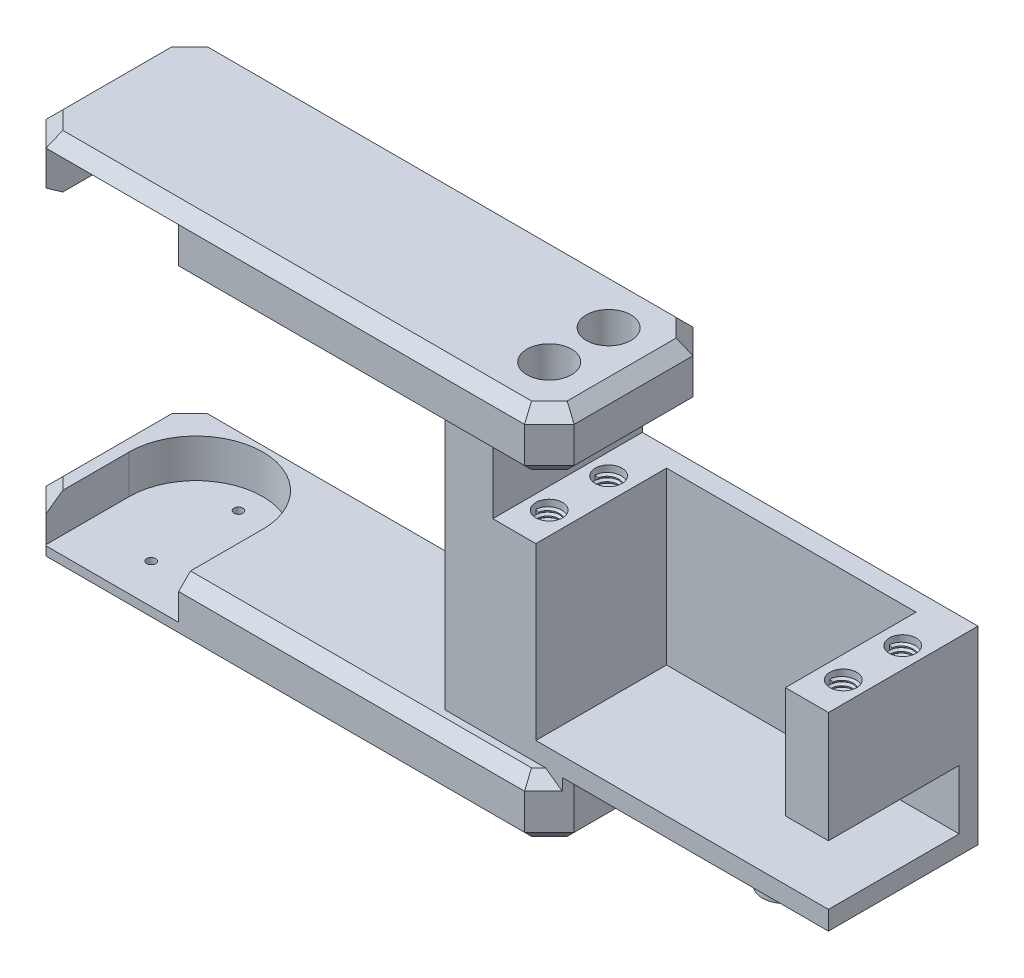
SolidWorks part; units mm, degrees
ref_plane "Front Plane" through (0, 0, 0) normal (0, 0, 1) x (1, 0, 0)
ref_plane "Top Plane" through (0, 0, 0) normal (0, 1, 0) x (1, 0, 0)
ref_plane "Right Plane" through (0, 0, 0) normal (1, 0, 0) x (0, 0, -1)
sketch "Sketch1" plane through (0, 0, 0) normal (0, 1, 0) x (1, 0, 0)
  line L0 (0, 11) -> (0, 14.175)
  line L1 (-21, -11) -> (21, -11) construction
  line L2 (-21, -11) -> (-21, 11)
  line L3 (-21, 11) -> (21, 11)
  line L4 (21, -11) -> (21, 11)
  line L5 (-21, -11) -> (21, 11) construction
  line L6 (-21, 11) -> (21, -11) construction
  line L7 (0, 0) -> (-20, 0) construction
  line L8 (-20, 0) -> (-27.25, 0) construction
  line L10 (-27.25, 14.175) -> (0, 14.175)
  line L11 (0, 0) -> (27.25, 0) construction
  line L13 (27.25, 14.175) -> (0, 14.175)
  line L14 (0, 14.175) -> (0, 16.3945)
  line L15 (0, 16.3945) -> (-24.75, 16.3945) construction
  line L16 (-24.75, 0) -> (-24.75, 5) construction
  line L17 (0, 16.3945) -> (24.75, 16.3945) construction
  line L18 (24.75, 0) -> (24.75, 5) construction
  line L19 (24.75, 0) -> (24.75, -5) construction
  line L20 (-24.75, 0) -> (-24.75, -5) construction
  line L22 (27.25, -11) -> (21, -11)
  line L25 (-27.25, -11) -> (-21, -11)
  line L27 (-28.25, 0) -> (-28.25, 14.175)
  line L28 (-28.25, 14.175) -> (-27.25, 14.175)
  line L29 (-27.25, -11) -> (-28.25, -11)
  line L30 (-28.25, -11) -> (-28.25, 0)
  line L31 (27.25, -11) -> (28.25, -11)
  line L32 (28.25, -11) -> (28.25, 0)
  line L33 (28.25, 0) -> (28.25, 14.175)
  line L34 (28.25, 14.175) -> (27.25, 14.175)
  point P0 (0, 0)
  dimension "D4" = 10
  dimension "D8" = 7.25
  dimension "D1" = 42
  dimension "D2" = 22
  dimension "D3" = 24.75
  dimension "D5" = 14.175
  dimension "D6" = 27.25
  dimension "D7" = 24.75
sketch "Sketch2" plane through (0, 0, 0) normal (0, 1, 0) x (1, 0, 0)
  line L0 (-27.25, -11) -> (27.25, -11)
  line L1 (27.25, -11) -> (27.25, 14.175)
  line L2 (27.25, 14.175) -> (-27.25, 14.175)
  line L3 (-27.25, 14.175) -> (-27.25, -11)
extrude "Boss-Extrude1" add sketch "Sketch2" along normal blind 3.175
extrude "Boss-Extrude2" add sketch "Sketch1" along normal blind 31.875
sketch "Sketch4" plane through (0, 31.875, 0) normal (0, 1, 0) x (1, 0, 0)
  line L0 (0, 0) -> (27.25, 0) construction
  line L1 (0, 0) -> (0, -11.8283) construction
  line L2 (0, -11.8283) -> (24.75, -11.8283) construction
  line L3 (24.75, 0) -> (24.75, -5) construction
  line L4 (24.75, 0) -> (24.75, 5) construction
  line L5 (0, 0) -> (-27.25, 0) construction
  line L6 (0, -11.8283) -> (-24.75, -11.8283) construction
  line L7 (-24.75, 0) -> (-24.75, -5) construction
  line L8 (-24.75, 0) -> (-24.75, 5) construction
  circle A0 centre (24.75, -5) radius 2.25
  circle A1 centre (24.75, 5) radius 2.25
  circle A2 centre (-24.75, -5) radius 2.25
  circle A3 centre (-24.75, 5) radius 2.25
  dimension "D1" = 24.75
extrude "Cut-Extrude1" cut sketch "Sketch4" against normal blind 12.7
thread "Thread1" pitch 0.7937 start angle 0, offset 1, length 0, pitch 0.7937, diameter 4.5
ref_plane "Plane1" through (-27, 30.875, -5) normal (0, 0, 1) x (-1, 0, 0)
sketch "Thread Profile1" plane through (-27, 30.875, -5) normal (0, 0, 1) x (-1, 0, 0)
  line L0 (0, 0) -> (0, 0.7937) construction
  line L11 (0, 0) -> (0, 0.6945)
  line L12 (0, 0.6945) -> (-0.4296, 0.4465)
  line L13 (-0.4296, 0.4465) -> (-0.4296, 0.248)
  line L15 (-0.4296, 0.248) -> (0, 0)
  line L17 (-0.4296, 0.3473) -> (0, 0.3473) construction
  point P2 (0, 0)
  dimension "Pitch" = 0.7937
  dimension "Profile_Angle" = 60
  dimension "Profile_Land" = 0.1984
  dimension "Profile_Height" = 0.4296
thread "Thread2" pitch 0.7937 profile "Thread Profile2" start angle 0, offset 1, length 0, pitch 0.7937, diameter 4.5
ref_plane "Plane2" through (-27, 30.875, 5) normal (0, 0, 1) x (-1, 0, 0)
sketch "Thread Profile2" plane through (-27, 30.875, 5) normal (0, 0, 1) x (-1, 0, 0)
  line L0 (0, 0) -> (0, 0.7937) construction
  line L11 (0, 0) -> (0, 0.6945)
  line L12 (0, 0.6945) -> (-0.4296, 0.4465)
  line L13 (-0.4296, 0.4465) -> (-0.4296, 0.248)
  line L15 (-0.4296, 0.248) -> (0, 0)
  line L17 (-0.4296, 0.3473) -> (0, 0.3473) construction
  point P2 (0, 0)
  dimension "Pitch" = 0.7937
  dimension "Profile_Angle" = 60
  dimension "Profile_Land" = 0.1984
  dimension "Profile_Height" = 0.4296
thread "Thread3" pitch 0.7937 profile "Thread Profile3" start angle 0, offset 1, length 0, pitch 0.7937, diameter 4.5
ref_plane "Plane3" through (22.5, 30.875, -5) normal (0, 0, 1) x (-1, 0, 0)
sketch "Thread Profile3" plane through (22.5, 30.875, -5) normal (0, 0, 1) x (-1, 0, 0)
  line L0 (0, 0) -> (0, 0.7937) construction
  line L11 (0, 0) -> (0, 0.6945)
  line L12 (0, 0.6945) -> (-0.4296, 0.4465)
  line L13 (-0.4296, 0.4465) -> (-0.4296, 0.248)
  line L15 (-0.4296, 0.248) -> (0, 0)
  line L17 (-0.4296, 0.3473) -> (0, 0.3473) construction
  point P2 (0, 0)
  dimension "Pitch" = 0.7937
  dimension "Profile_Angle" = 60
  dimension "Profile_Land" = 0.1984
  dimension "Profile_Height" = 0.4296
thread "Thread4" pitch 0.7937 profile "Thread Profile4" start angle 0, offset 1, length 0, pitch 0.7937, diameter 4.5
ref_plane "Plane4" through (22.5, 30.875, 5) normal (0, 0, 1) x (-1, 0, 0)
sketch "Thread Profile4" plane through (22.5, 30.875, 5) normal (0, 0, 1) x (-1, 0, 0)
  line L0 (0, 0) -> (0, 0.7937) construction
  line L11 (0, 0) -> (0, 0.6945)
  line L12 (0, 0.6945) -> (-0.4296, 0.4465)
  line L13 (-0.4296, 0.4465) -> (-0.4296, 0.248)
  line L15 (-0.4296, 0.248) -> (0, 0)
  line L17 (-0.4296, 0.3473) -> (0, 0.3473) construction
  point P2 (0, 0)
  dimension "Pitch" = 0.7937
  dimension "Profile_Angle" = 60
  dimension "Profile_Land" = 0.1984
  dimension "Profile_Height" = 0.4296
sketch "Sketch13" plane through (21, 0, 0) normal (-1, 0, 0) x (0, 0, 1)
  line L0 (11, 3.175) -> (11, 13.175)
  line L1 (11, 31.875) -> (11, 0) construction
  line L2 (11, 13.175) -> (-11, 13.175)
  line L3 (-11, 31.875) -> (-11, 3.175) construction
  line L4 (-11, 13.175) -> (-11, 3.175)
  line L5 (-11, 3.175) -> (11, 3.175)
  dimension "D1" = 10
extrude "Cut-Extrude2" cut sketch "Sketch13" against normal blind 12.7
sketch "Sketch14" plane through (0, 0, 0) normal (0, -1, 0) x (1, 0, 0)
  line L0 (20, 0) -> (9.9, 0) construction
  line L1 (20, 0) -> (20, 1.8391) construction
  circle A1 centre (9.9, 0) radius 3.75
  dimension "D1" = 7.5
extrude "Boss-Extrude3" add sketch "Sketch14" along normal blind 8
sketch "Sketch15" plane through (-28.25, 0, 0) normal (-1, 0, 0) x (0, 0, 1)
  line L4 (-14.175, 0) -> (11, 0)
  line L5 (11, 0) -> (-14.175, 0) construction
  line L6 (11, 31.875) -> (11, 0) construction
  line L11 (7.1008, 47.975) -> (0, 47.975) construction
  line L13 (0, 47.975) -> (0, -8) construction
  line L14 (-3.75, -8) -> (3.75, -8) construction
  line L15 (3.75, 0) -> (3.75, -8) construction
  line L17 (7.1008, 47.975) -> (9.7473, 47.975) construction
  line L21 (7.1008, 3.175) -> (7.1008, 47.975) construction
  line L22 (-11, 3.175) -> (11, 3.175) construction
  line L24 (9.7473, 47.975) -> (9.7473, 43.475) construction
  line L25 (9.7473, 43.475) -> (11, 43.475) construction
  line L26 (11, 43.475) -> (11, 0)
  line L27 (11, 43.475) -> (-14.175, 43.475)
  line L28 (-14.175, 43.475) -> (-14.175, 0)
  line L29 (3.75, -8) -> (3.75, 0) construction
  line L30 (0, 19.9875) -> (30.891, 19.9875) construction
  line L31 (7.1008, 3.175) -> (7.1008, 0) construction
  dimension "D1" = 4.5
  dimension "D5" = 3.175
  dimension "D2" = 55.975
  dimension "D3" = 44.8
  dimension "D4" = 8
extrude "Boss-Extrude4" add sketch "Sketch15" along normal blind 20 contours L28 L4 L26 L27
sketch "Sketch16" plane through (0, 43.475, 0) normal (0, 1, 0) x (1, 0, 0)
  line L0 (9.9, 0) -> (-28.25, 0) construction
  line L1 (-28.25, -11) -> (-28.25, 14.175) construction
  line L2 (-104.45, 0) -> (-15.55, 0) construction
  line L3 (-48.25, -11) -> (-48.25, 14.175) construction
  line L9 (-104.45, 0) -> (-104.45, 10)
  line L10 (-104.45, 0) -> (-104.45, -10)
  line L23 (-15.55, 0) -> (-15.55, 10)
  line L24 (-19.725, 14.175) -> (-100.275, 14.175)
  line L25 (-104.45, -10) -> (-100.275, -14.175)
  line L26 (-15.55, 10) -> (-19.725, 14.175)
  line L27 (-104.45, 10) -> (-100.275, 14.175)
  line L28 (-15.55, 0) -> (-15.55, -10)
  line L29 (-100.275, -14.175) -> (-19.725, -14.175)
  line L30 (-15.55, -10) -> (-19.725, -14.175)
  circle A0 centre (-48.25, 0) radius 11.25 construction
  circle A2 centre (9.9, 0) radius 11.25 construction
  dimension "D1" = 88.9
extrude "Boss-Extrude5" add sketch "Sketch16" along normal blind 10
sketch "Sketch20" plane through (0, 53.475, 0) normal (0, 1, 0) x (1, 0, 0)
  circle A0 centre (-24.75, 5) radius 3.75
  circle A1 centre (-24.75, -5) radius 3.75
extrude "Cut-Extrude3" cut sketch "Sketch20" against normal blind 10
sketch "Sketch21" plane through (0, 0, 0) normal (0, -1, 0) x (1, 0, 0)
  line L0 (-19.725, 14.175) -> (-100.275, 14.175)
  line L1 (-100.275, 14.175) -> (-104.45, 10)
  line L2 (-104.45, 10) -> (-104.45, -10)
  line L3 (-104.45, -10) -> (-100.275, -14.175)
  line L4 (-100.275, -14.175) -> (-19.725, -14.175)
  line L5 (-19.725, -14.175) -> (-15.55, -10)
  line L6 (-15.55, -10) -> (-15.55, 10)
  line L7 (-15.55, 10) -> (-19.725, 14.175)
extrude "Boss-Extrude8" add sketch "Sketch21" along normal blind 10
sketch "Sketch22" plane through (0, 43.475, 0) normal (0, -1, 0) x (1, 0, 0)
  line L0 (-104.45, 0) -> (-100.45, 0) construction
  line L1 (-104.45, 10) -> (-104.45, -10) construction
  line L2 (-100.45, 0) -> (-89.2, 0) construction
  circle A0 centre (-89.2, 0) radius 11.25
extrude "Cut-Extrude4" cut sketch "Sketch22" against normal blind 8
sketch "Sketch23" plane through (0, 0, 0) normal (0, 1, 0) x (1, 0, 0)
  circle A0 centre (-89.2, 0) radius 11.25
extrude "Cut-Extrude5" cut sketch "Sketch23" against normal blind 6.505
chamfer "Chamfer2" distance 2 angle 45 31 edges at (-60, 53.475, 14.175) (-102.3625, 53.475, 12.0875) (-104.45, 53.475, 0) (-102.3625, 53.475, -12.0875) (-60, 53.475, -14.175) (-15.55, 53.475, 0) (-17.6375, 53.475, -12.0875) (-17.6375, -10, 12.0875) (-15.55, -10, 0) (-17.6375, -10, -12.0875) (-60, -10, -14.175) (-102.3625, -10, -12.0875) (-104.45, -10, 0) (-102.3625, -10, 12.0875) (-23.9875, 43.475, -14.175) (-17.6375, 43.475, -12.0875) (-15.55, 43.475, 0) (-17.6375, 43.475, 12.0875) (-60, 43.475, 14.175) (-102.3625, 43.475, 12.0875) (-104.45, 43.475, 0) (-102.3625, 43.475, -12.0875) (-74.2625, 43.475, -14.175) (-18.1375, 0, 12.5875) (-60, 0, 14.175) (-102.3625, 0, 12.0875) (-104.45, 0, 0) (-102.3625, 0, -12.0875) (-74.2625, 0, -14.175) (-60, -10, 14.175) (-17.6375, 53.475, 12.0875)
sketch "Sketch24" plane through (0, -6.505, 0) normal (0, 1, 0) x (1, 0, 0)
  line L0 (-100.45, 0) -> (-100.45, -17.477)
  line L1 (-100.45, -17.477) -> (-77.95, -17.477)
  line L2 (-77.95, -17.477) -> (-77.95, 0)
  line L3 (-77.95, 0) -> (-100.45, 0)
  circle A0 centre (-89.2, 0) radius 11.25 construction
extrude "Cut-Extrude6" cut sketch "Sketch24" along normal blind 10
sketch "Sketch25" plane through (0, 51.475, 0) normal (0, -1, 0) x (1, 0, 0)
  line L0 (-100.45, 0) -> (-77.95, 0)
  line L1 (-77.95, 0) -> (-77.95, 20.3304)
  line L2 (-77.95, 20.3304) -> (-100.45, 20.3304)
  line L3 (-100.45, 20.3304) -> (-100.45, 0)
extrude "Cut-Extrude7" cut sketch "Sketch25" along normal blind 10
chamfer "Chamfer3" distance 12 angle 45 2 edges at (-48.25, 21.7375, -14.175) (-48.25, 21.7375, 11)
sketch "Sketch28" plane through (0, -6.505, 0) normal (0, 1, 0) x (1, 0, 0)
  line L0 (-89.2, 0) -> (-89.2, 6.4) construction
  line L1 (-89.2, 0) -> (-89.2, -6.8) construction
  line L2 (-89.2, -6.8) -> (-89.2, -7.55) construction
  line L3 (-89.2, 6.4) -> (-89.2, 7.15) construction
  circle A0 centre (-89.2, 0) radius 10.25 construction
  circle A3 centre (-89.2, -7.55) radius 0.75
  circle A4 centre (-89.2, 7.15) radius 0.75
  dimension "D1" = 20.5
extrude "Cut-Extrude8" cut sketch "Sketch28" against normal blind 10
sketch "Sketch29" plane through (0, 0, 0) normal (0, 0, 1) x (1, 0, 0)
  line L0 (-89.1125, -6.505) -> (-89.1125, 38.295) construction
  line L1 (-100.275, -6.505) -> (-77.95, -6.505) construction
  line L2 (-89.1125, 38.295) -> (-89.1125, 41.47) construction
  line L5 (-92.5783, 51.475) -> (-92.5783, -4.505) construction
  line L6 (-77.95, 51.475) -> (-100.275, 51.475) construction
  line L7 (-86.1012, -6.505) -> (-86.1012, 3.495) construction
  line L8 (-86.1012, 3.495) -> (-86.1012, 40.295) construction
  line L9 (-86.1012, 40.295) -> (-86.1012, 43.475) construction
  line L10 (-100.45, 43.475) -> (-77.95, 43.475) construction
  line L11 (-100.45, 0) -> (-100.45, 43.475) construction
  line L12 (-100.45, 21.7375) -> (-59.741, 21.7375) construction
  dimension "D1" = 55.98
  dimension "D2" = 44.8
  dimension "D3" = 3.175
  dimension "D4" = 10
  dimension "D5" = 36.8
  dimension "D6" = 43.475
  dimension "D7" = 18.2425
  dimension "D8" = 18.5575
  dimension "D9" = 3.18
